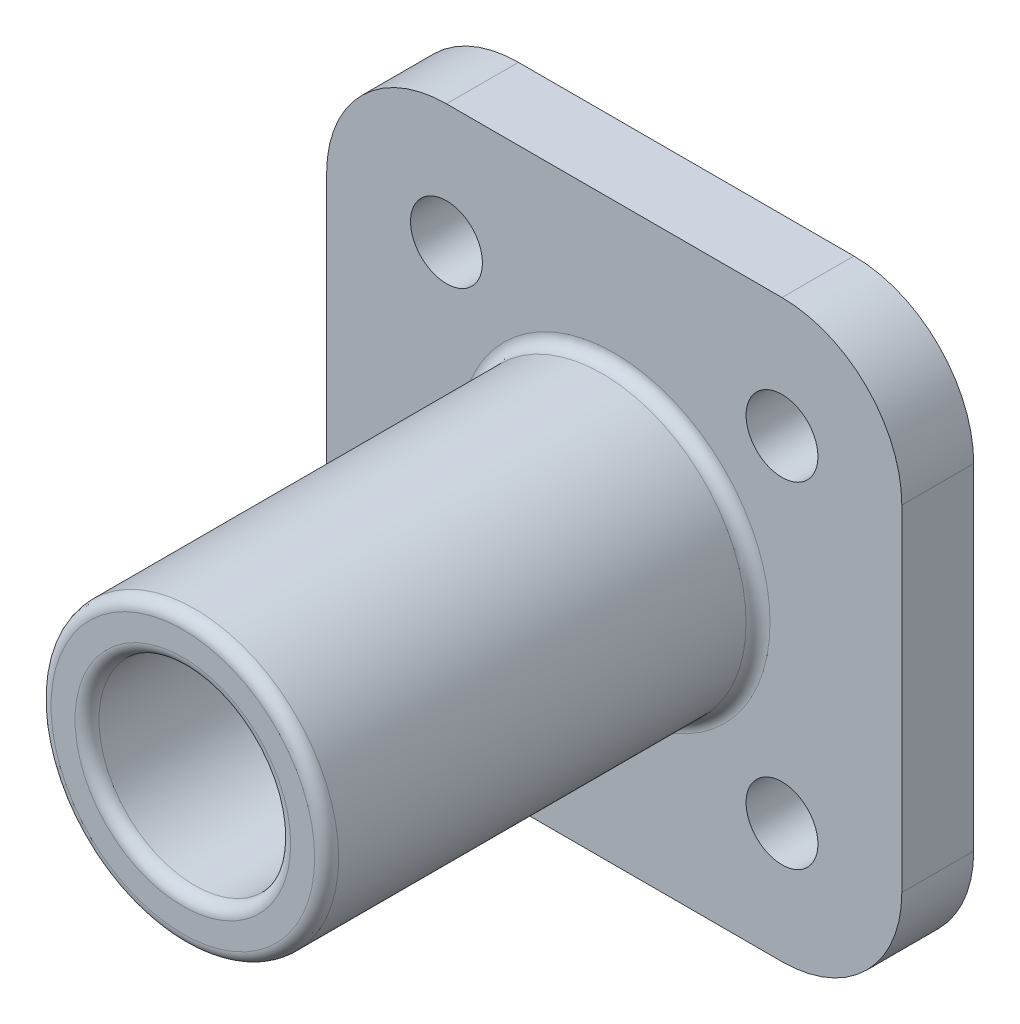
SolidWorks part; units mm, degrees
ref_plane "Plan de face" through (0, 0, 0) normal (0, 0, 1) x (1, 0, 0)
ref_plane "Plan de dessus" through (0, 0, 0) normal (0, 1, 0) x (1, 0, 0)
ref_plane "Plan de droite" through (0, 0, 0) normal (1, 0, 0) x (0, 0, -1)
sketch "Esquisse1" plane through (0, 0, 0) normal (0, 0, 1) x (1, 0, 0)
  line L0 (-7, 7) -> (7, 7) construction
  line L1 (7, -12) -> (-7, -12)
  line L2 (12, -7) -> (12, 7)
  line L3 (7, 12) -> (-7, 12)
  line L4 (-12, -7) -> (-12, 7)
  line L5 (12, -12) -> (-12, 12) construction
  line L6 (12, 12) -> (-12, -12) construction
  line L7 (-7, 7) -> (-7, -7) construction
  arc A0 (7, -12) -> (12, -7) centre (7, -7) ccw
  arc A1 (-7, -12) -> (-12, -7) centre (-7, -7) cw
  arc A2 (12, 7) -> (7, 12) centre (7, 7) ccw
  arc A3 (-7, 12) -> (-12, 7) centre (-7, 7) ccw
  circle A4 centre (-7, 7) radius 1.5
  circle A5 centre (7, 7) radius 1.5
  circle A6 centre (7, -7) radius 1.5
  circle A7 centre (-7, -7) radius 1.5
  point P0 (0, 0)
  dimension "D2" = 5
  dimension "D3" = 3
  dimension "D1" = 14
  dimension "D6" = 14
  dimension "D7" = 14
  dimension "D4" = 2
  dimension "D5" = 2
extrude "Boss.-Extru.1" add sketch "Esquisse1" along normal blind 3
sketch "Esquisse2" plane through (0, 0, 3) normal (0, 0, 1) x (1, 0, 0)
  circle A0 centre (0, 0) radius 6
  circle A1 centre (0, 0) radius 4
  dimension "D1" = 8
  dimension "D2" = 12
extrude "Boss.-Extru.2" add sketch "Esquisse2" along normal blind 18 contours A0 | A1
fillet "Congé1" radius 0.5 3 edges at (6, 0, 3) (6, 0, 21) (4, 0, 21)
